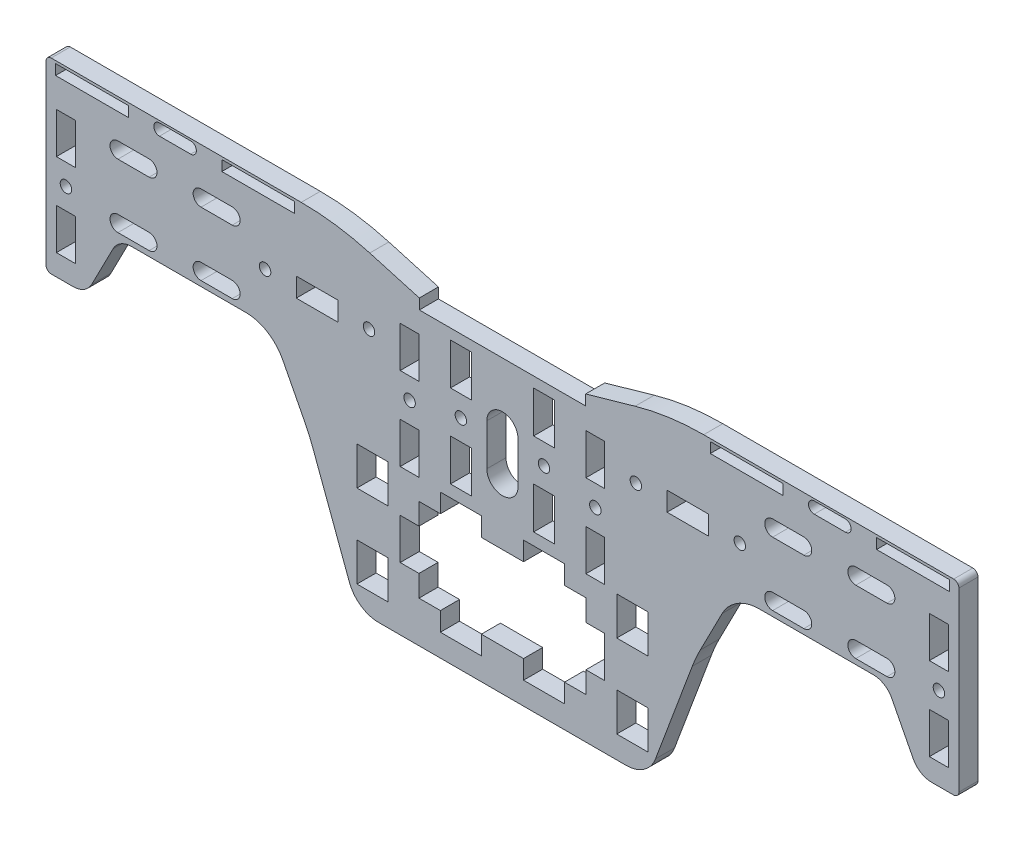
SolidWorks part; units mm, degrees
ref_plane "Front Plane" through (0, 0, 0) normal (0, 0, 1) x (1, 0, 0)
ref_plane "Top Plane" through (0, 0, 0) normal (0, 1, 0) x (1, 0, 0)
ref_plane "Right Plane" through (0, 0, 0) normal (1, 0, 0) x (0, 0, -1)
sketch "Sketch1" plane through (0, 0, 0) normal (0, 0, 1) x (1, 0, 0)
  line L0 (25.4, 66.675) -> (-25.4, 66.675) construction
  line L1 (25.5, -12.8) -> (18.95, -12.8)
  line L2 (25.5, -12.8) -> (25.5, -6.25)
  line L3 (-25.5, 12.8) -> (-18.95, 12.8)
  line L4 (-25.5, -12.8) -> (-25.5, -6.25)
  line L5 (25.5, -12.8) -> (-25.5, 12.8) construction
  line L6 (25.5, 12.8) -> (-25.5, -12.8) construction
  line L7 (0, 0) -> (0, 66.675) construction
  line L8 (25.4, 63.5) -> (-25.4, 63.5)
  line L9 (95.25, 101.6) -> (95.25, -30.1359) construction
  line L10 (19.05, 101.6) -> (171.45, 101.6) construction
  line L11 (171.45, 122.2375) -> (19.05, 122.2375) construction
  line L12 (171.45, 122.2375) -> (171.45, 80.9625) construction
  line L13 (171.45, 80.9625) -> (112.7125, 80.9625) construction
  line L14 (19.05, 122.2375) -> (19.05, 80.9625) construction
  line L15 (171.45, 122.2375) -> (19.05, 80.9625) construction
  line L16 (171.45, 80.9625) -> (19.05, 122.2375) construction
  line L17 (77.7875, 80.9625) -> (19.05, 80.9625) construction
  line L18 (77.7875, 69.9655) -> (74.2442, 69.9655) construction
  line L19 (112.7125, 69.9655) -> (112.7125, 80.9625) construction
  line L20 (63.246, 14.9745) -> (74.2442, 36.3359) construction
  line L21 (77.7875, 69.9655) -> (77.7875, 80.9625) construction
  line L22 (112.7125, 69.9655) -> (77.7875, 80.9625) construction
  line L23 (112.7125, 80.9625) -> (77.7875, 69.9655) construction
  line L24 (116.2558, 36.3359) -> (74.2442, 36.3359) construction
  line L25 (116.2558, 36.3359) -> (116.2558, 69.9655) construction
  line L26 (116.2558, 69.9655) -> (112.7125, 69.9655) construction
  line L27 (74.2442, 36.3359) -> (74.2442, 69.9655) construction
  line L28 (116.2558, 36.3359) -> (74.2442, 69.9655) construction
  line L29 (116.2558, 69.9655) -> (74.2442, 36.3359) construction
  line L30 (127.254, -75.2463) -> (63.246, -75.2463) construction
  line L31 (127.254, -75.2463) -> (127.254, 14.9745) construction
  line L32 (127.254, 14.9745) -> (63.246, 14.9745) construction
  line L33 (63.246, -75.2463) -> (63.246, 14.9745) construction
  line L34 (127.254, -75.2463) -> (63.246, 14.9745) construction
  line L35 (127.254, 14.9745) -> (63.246, -75.2463) construction
  line L36 (127.254, 14.9745) -> (116.2558, 36.3359) construction
  line L37 (74.2442, 59.7801) -> (116.2558, 59.7801) construction
  line L38 (74.2442, 40.3491) -> (116.2558, 40.3491) construction
  line L39 (-6.45, 12.8) -> (6.45, 12.8)
  line L40 (-6.45, 18.542) -> (-18.95, 18.542)
  line L41 (-6.45, 18.542) -> (-6.45, 12.8)
  line L42 (18.95, 18.542) -> (18.95, 12.8)
  line L43 (-18.95, 18.542) -> (-18.95, 12.8)
  line L44 (-6.45, 18.542) -> (-18.95, 12.8) construction
  line L45 (-6.45, 12.8) -> (-18.95, 18.542) construction
  line L46 (-25.5, 0) -> (25.5, 0) construction
  line L47 (6.45, 18.542) -> (6.45, 12.8)
  line L48 (6.45, 18.542) -> (18.95, 12.8) construction
  line L49 (6.45, 12.8) -> (18.95, 18.542) construction
  line L50 (6.45, 18.542) -> (18.95, 18.542)
  line L51 (18.95, 12.8) -> (25.5, 12.8)
  line L52 (44.45, -6.858) -> (34.925, -18.542) construction
  line L53 (44.45, 18.542) -> (34.925, 18.542)
  line L54 (44.45, 18.542) -> (44.45, 6.858)
  line L55 (44.45, 6.858) -> (34.925, 6.858)
  line L56 (34.925, 18.542) -> (34.925, 6.858)
  line L57 (44.45, 18.542) -> (34.925, 6.858) construction
  line L58 (44.45, 6.858) -> (34.925, 18.542) construction
  line L59 (44.45, -18.542) -> (34.925, -6.858) construction
  line L60 (34.925, -18.542) -> (34.925, -6.858)
  line L61 (44.45, -6.858) -> (34.925, -6.858)
  line L62 (44.45, -18.542) -> (44.45, -6.858)
  line L63 (44.45, -18.542) -> (34.925, -18.542)
  line L64 (-44.45, -18.542) -> (-34.925, -6.858) construction
  line L65 (-44.45, 6.858) -> (-34.925, 18.542) construction
  line L66 (-44.45, 18.542) -> (-34.925, 6.858) construction
  line L67 (0, 0) -> (0, -30.1681) construction
  line L68 (-44.45, -6.858) -> (-34.925, -18.542) construction
  line L69 (-44.45, -18.542) -> (-34.925, -18.542)
  line L70 (-44.45, -18.542) -> (-44.45, -6.858)
  line L71 (-44.45, -6.858) -> (-34.925, -6.858)
  line L72 (-34.925, -18.542) -> (-34.925, -6.858)
  line L73 (-34.925, 18.542) -> (-34.925, 6.858)
  line L74 (6.45, -12.8) -> (18.95, -18.542) construction
  line L75 (6.45, -18.542) -> (18.95, -12.8) construction
  line L76 (-6.45, -12.8) -> (-18.95, -18.542) construction
  line L77 (-6.45, -18.542) -> (-18.95, -12.8) construction
  line L78 (-44.45, 6.858) -> (-34.925, 6.858)
  line L79 (44.45, -25.4) -> (-44.45, -25.4)
  line L80 (-44.45, 18.542) -> (-44.45, 6.858)
  line L81 (-44.45, 18.542) -> (-34.925, 18.542)
  line L82 (-12.7, 63.5) -> (-12.7, 47.625) construction
  line L83 (-15.875, 22.225) -> (-9.525, 22.225)
  line L84 (-15.875, 47.625) -> (-9.525, 47.625)
  line L85 (-15.875, 47.625) -> (-15.875, 60.325)
  line L86 (-15.875, 60.325) -> (-9.525, 60.325)
  line L87 (-9.525, 47.625) -> (-9.525, 60.325)
  line L88 (-15.875, 47.625) -> (-9.525, 60.325) construction
  line L89 (-15.875, 60.325) -> (-9.525, 47.625) construction
  line L90 (6.45, -18.542) -> (18.95, -18.542)
  line L91 (6.45, -18.542) -> (6.45, -12.8)
  line L92 (-18.95, -18.542) -> (-18.95, -12.8)
  line L93 (18.95, -18.542) -> (18.95, -12.8)
  line L94 (-6.45, -18.542) -> (-6.45, -12.8)
  line L95 (-6.45, -18.542) -> (-18.95, -18.542)
  line L96 (-18.95, -12.8) -> (-25.5, -12.8)
  line L97 (6.45, -12.8) -> (-6.45, -12.8)
  line L98 (-25.5, 6.25) -> (-25.5, 12.8)
  line L99 (-31.242, -6.25) -> (-25.5, -6.25)
  line L100 (-31.242, -6.25) -> (-31.242, 6.25)
  line L101 (-31.242, 6.25) -> (-25.5, 6.25)
  line L102 (31.242, 6.25) -> (25.5, 6.25)
  line L103 (-31.242, -6.25) -> (-25.5, 6.25) construction
  line L104 (-31.242, 6.25) -> (-25.5, -6.25) construction
  line L105 (31.242, -6.25) -> (25.5, -6.25)
  line L106 (31.242, -6.25) -> (25.5, 6.25) construction
  line L107 (31.242, 6.25) -> (25.5, -6.25) construction
  line L108 (31.242, -6.25) -> (31.242, 6.25)
  line L109 (25.5, 6.25) -> (25.5, 12.8)
  line L110 (-15.875, 22.225) -> (-15.875, 34.925)
  line L111 (-15.875, 34.925) -> (-9.525, 34.925)
  line L112 (82.55, 59.7801) -> (92.075, 59.7801) construction
  line L113 (82.55, 62.1931) -> (92.075, 62.1931)
  line L114 (82.55, 57.3671) -> (92.075, 57.3671)
  line L115 (82.55, 40.3491) -> (92.075, 40.3491) construction
  line L116 (82.55, 42.7621) -> (92.075, 42.7621)
  line L117 (82.55, 37.9361) -> (92.075, 37.9361)
  line L118 (107.95, 59.7801) -> (117.475, 59.7801) construction
  line L119 (107.95, 62.1931) -> (117.475, 62.1931)
  line L120 (107.95, 57.3671) -> (117.475, 57.3671)
  line L121 (107.95, 40.3491) -> (117.475, 40.3491) construction
  line L122 (107.95, 42.7621) -> (117.475, 42.7621)
  line L123 (107.95, 37.9361) -> (117.475, 37.9361)
  line L124 (63.8955, 73.1405) -> (128.9432, 73.1405) construction
  line L125 (63.5, 73.1405) -> (76.2, 73.1405)
  line L126 (63.5, 73.1405) -> (63.5, 69.9655)
  line L127 (114.3, 73.1405) -> (127, 73.1405)
  line L128 (63.5, 69.9655) -> (76.2, 69.9655)
  line L129 (63.5, 69.9655) -> (76.2, 73.1405) construction
  line L130 (63.5, 73.1405) -> (76.2, 69.9655) construction
  line L131 (114.3, 69.9655) -> (127, 69.9655)
  line L132 (76.2, 73.1405) -> (85.725, 73.1405)
  line L133 (76.2, 69.9655) -> (85.725, 69.9655)
  line L134 (85.725, 73.1405) -> (85.725, 69.9655)
  line L135 (114.3, 73.1405) -> (114.3, 69.9655)
  line L136 (127, 73.1405) -> (136.525, 73.1405)
  line L137 (136.525, 73.1405) -> (136.525, 69.9655)
  line L138 (127, 69.9655) -> (136.525, 69.9655)
  line L139 (-28.371, 0) -> (-28.371, 63.5) construction
  line L140 (-31.242, 44.55) -> (-25.5, 44.55)
  line L141 (-31.242, 31.65) -> (-25.5, 31.65)
  line L142 (-31.242, 31.65) -> (-31.242, 19.15)
  line L143 (-31.242, 19.15) -> (-25.5, 19.15)
  line L144 (-25.5, 31.65) -> (-25.5, 19.15)
  line L145 (-31.242, 31.65) -> (-25.5, 19.15) construction
  line L146 (-31.242, 19.15) -> (-25.5, 31.65) construction
  line L147 (-31.242, 57.05) -> (-31.242, 44.55)
  line L148 (-31.242, 57.05) -> (-25.5, 57.05)
  line L149 (-25.5, 57.05) -> (-25.5, 44.55)
  line L150 (28.371, 0) -> (28.371, 63.5) construction
  line L151 (31.242, 19.15) -> (25.5, 31.65) construction
  line L152 (31.242, 31.65) -> (25.5, 19.15) construction
  line L153 (25.5, 57.05) -> (25.5, 44.55)
  line L154 (31.242, 57.05) -> (25.5, 57.05)
  line L155 (31.242, 57.05) -> (31.242, 44.55)
  line L156 (25.5, 31.65) -> (25.5, 19.15)
  line L157 (31.242, 19.15) -> (25.5, 19.15)
  line L158 (31.242, 31.65) -> (31.242, 19.15)
  line L159 (31.242, 31.65) -> (25.5, 31.65)
  line L160 (31.242, 44.55) -> (25.5, 44.55)
  line L161 (50.8, 73.9342) -> (139.446, 73.9342)
  line L162 (25.4, 63.5) -> (25.4, 66.675)
  line L163 (25.4, 66.675) -> (50.8, 73.9342)
  line L164 (44.45, -25.4) -> (59.0461, 13.7533)
  line L165 (70.6731, 36.3359) -> (117.1876, 36.3359)
  line L166 (59.0461, 13.7533) -> (70.6731, 36.3359)
  line L167 (133.35, 73.9342) -> (133.35, 48.6342) construction
  line L168 (60.4232, 16.4279) -> (71.4214, 37.7893) construction
  line L169 (130.429, 35.7342) -> (136.271, 35.7342)
  line L170 (-25.4, 63.5) -> (-25.4, 66.675)
  line L171 (-25.4, 66.675) -> (-50.8, 73.9342)
  line L172 (-63.5, 73.1405) -> (-76.2, 69.9655) construction
  line L173 (-63.5, 69.9655) -> (-76.2, 73.1405) construction
  line L174 (-63.8955, 73.1405) -> (-128.9432, 73.1405) construction
  line L175 (-74.2442, 40.3491) -> (-116.2558, 40.3491) construction
  line L176 (-74.2442, 59.7801) -> (-116.2558, 59.7801) construction
  line L177 (-127.254, 14.9745) -> (-116.2558, 36.3359) construction
  line L178 (-127.254, 14.9745) -> (-63.246, -75.2463) construction
  line L179 (-127.254, -75.2463) -> (-63.246, 14.9745) construction
  line L180 (-63.246, -75.2463) -> (-63.246, 14.9745) construction
  line L181 (-127.254, 14.9745) -> (-63.246, 14.9745) construction
  line L182 (-127.254, -75.2463) -> (-127.254, 14.9745) construction
  line L183 (-127.254, -75.2463) -> (-63.246, -75.2463) construction
  line L184 (-116.2558, 69.9655) -> (-74.2442, 36.3359) construction
  line L185 (-116.2558, 36.3359) -> (-74.2442, 69.9655) construction
  line L186 (-74.2442, 36.3359) -> (-74.2442, 69.9655) construction
  line L187 (-116.2558, 69.9655) -> (-112.7125, 69.9655) construction
  line L188 (-116.2558, 36.3359) -> (-116.2558, 69.9655) construction
  line L189 (-116.2558, 36.3359) -> (-74.2442, 36.3359) construction
  line L190 (-112.7125, 80.9625) -> (-77.7875, 69.9655) construction
  line L191 (-112.7125, 69.9655) -> (-77.7875, 80.9625) construction
  line L192 (-77.7875, 69.9655) -> (-77.7875, 80.9625) construction
  line L193 (-63.246, 14.9745) -> (-74.2442, 36.3359) construction
  line L194 (-112.7125, 69.9655) -> (-112.7125, 80.9625) construction
  line L195 (-77.7875, 69.9655) -> (-74.2442, 69.9655) construction
  line L196 (-77.7875, 80.9625) -> (-19.05, 80.9625) construction
  line L197 (-171.45, 80.9625) -> (-19.05, 122.2375) construction
  line L198 (-171.45, 122.2375) -> (-19.05, 80.9625) construction
  line L199 (-171.45, 80.9625) -> (-112.7125, 80.9625) construction
  line L200 (-171.45, 122.2375) -> (-171.45, 80.9625) construction
  line L201 (-171.45, 122.2375) -> (-19.05, 122.2375) construction
  line L202 (-19.05, 101.6) -> (-171.45, 101.6) construction
  line L203 (-95.25, 101.6) -> (-95.25, -30.1359) construction
  line L204 (130.429, 61.1342) -> (136.271, 61.1342)
  line L205 (130.429, 61.1342) -> (130.429, 48.6342)
  line L206 (-59.0461, 13.7533) -> (-70.6731, 36.3359)
  line L207 (-70.6731, 36.3359) -> (-117.1876, 36.3359)
  line L208 (-44.45, -25.4) -> (-59.0461, 13.7533)
  line L209 (-50.8, 73.9342) -> (-139.446, 73.9342)
  line L210 (-127, 69.9655) -> (-136.525, 69.9655)
  line L211 (-136.525, 73.1405) -> (-136.525, 69.9655)
  line L212 (-127, 73.1405) -> (-136.525, 73.1405)
  line L213 (-114.3, 73.1405) -> (-114.3, 69.9655)
  line L214 (-85.725, 73.1405) -> (-85.725, 69.9655)
  line L215 (-76.2, 69.9655) -> (-85.725, 69.9655)
  line L216 (-76.2, 73.1405) -> (-85.725, 73.1405)
  line L217 (-114.3, 69.9655) -> (-127, 69.9655)
  line L218 (-63.5, 69.9655) -> (-76.2, 69.9655)
  line L219 (-114.3, 73.1405) -> (-127, 73.1405)
  line L220 (-63.5, 73.1405) -> (-63.5, 69.9655)
  line L221 (-63.5, 73.1405) -> (-76.2, 73.1405)
  line L222 (-107.95, 40.3491) -> (-117.475, 40.3491) construction
  line L223 (-107.95, 42.7621) -> (-117.475, 42.7621)
  line L224 (-107.95, 37.9361) -> (-117.475, 37.9361)
  line L225 (-107.95, 59.7801) -> (-117.475, 59.7801) construction
  line L226 (-107.95, 62.1931) -> (-117.475, 62.1931)
  line L227 (-107.95, 57.3671) -> (-117.475, 57.3671)
  line L228 (-82.55, 40.3491) -> (-92.075, 40.3491) construction
  line L229 (-82.55, 42.7621) -> (-92.075, 42.7621)
  line L230 (-82.55, 37.9361) -> (-92.075, 37.9361)
  line L231 (-82.55, 59.7801) -> (-92.075, 59.7801) construction
  line L232 (-82.55, 62.1931) -> (-92.075, 62.1931)
  line L233 (-82.55, 57.3671) -> (-92.075, 57.3671)
  line L234 (-19.05, 122.2375) -> (-19.05, 80.9625) construction
  line L235 (-25.5, 44.55) -> (-25.5, 31.65) construction
  line L236 (25.5, 31.65) -> (25.5, 44.55) construction
  line L237 (-25.5, 38.1) -> (25.5, 38.1) construction
  line L238 (-9.525, 22.225) -> (-9.525, 34.925)
  line L239 (-15.875, 22.225) -> (-9.525, 34.925) construction
  line L240 (-15.875, 34.925) -> (-9.525, 22.225) construction
  line L241 (-12.7, 34.925) -> (-12.7, 18.542) construction
  line L242 (-12.7, 47.625) -> (-12.7, 34.925) construction
  line L243 (12.7, 47.625) -> (12.7, 34.925) construction
  line L244 (15.875, 34.925) -> (9.525, 22.225) construction
  line L245 (15.875, 22.225) -> (9.525, 34.925) construction
  line L246 (15.875, 60.325) -> (9.525, 47.625) construction
  line L247 (15.875, 47.625) -> (9.525, 60.325) construction
  line L248 (9.525, 22.225) -> (9.525, 34.925)
  line L249 (15.875, 34.925) -> (9.525, 34.925)
  line L250 (15.875, 22.225) -> (15.875, 34.925)
  line L251 (9.525, 47.625) -> (9.525, 60.325)
  line L252 (15.875, 60.325) -> (9.525, 60.325)
  line L253 (15.875, 47.625) -> (15.875, 60.325)
  line L254 (15.875, 47.625) -> (9.525, 47.625)
  line L255 (15.875, 22.225) -> (9.525, 22.225)
  line L256 (-116.2558, 50.75) -> (-74.2442, 50.75) construction
  line L257 (-85.725, 71.553) -> (-114.3, 71.553) construction
  line L258 (-95.25, 71.553) -> (-104.775, 71.553) construction
  line L259 (-95.25, 69.8004) -> (-104.775, 69.8004)
  line L260 (-95.25, 73.3056) -> (-104.775, 73.3056)
  line L261 (50.292, 53.671) -> (50.292, 47.829)
  line L262 (-62.992, 53.671) -> (-50.292, 53.671)
  line L263 (-62.992, 53.671) -> (-62.992, 47.829)
  line L264 (-62.992, 47.829) -> (-50.292, 47.829)
  line L265 (-50.292, 53.671) -> (-50.292, 47.829)
  line L266 (-62.992, 53.671) -> (-50.292, 47.829) construction
  line L267 (-62.992, 47.829) -> (-50.292, 53.671) construction
  line L268 (62.992, 53.671) -> (50.292, 47.829) construction
  line L269 (62.992, 47.829) -> (50.292, 53.671) construction
  line L270 (62.992, 47.829) -> (50.292, 47.829)
  line L271 (62.992, 53.671) -> (62.992, 47.829)
  line L272 (62.992, 53.671) -> (50.292, 53.671)
  line L273 (95.25, 71.553) -> (104.775, 71.553) construction
  line L274 (95.25, 69.8004) -> (104.775, 69.8004)
  line L275 (95.25, 73.3056) -> (104.775, 73.3056)
  line L276 (-56.642, 47.829) -> (-56.642, 53.671) construction
  line L277 (130.429, 48.6342) -> (136.271, 48.6342)
  line L278 (136.271, 61.1342) -> (136.271, 48.6342)
  line L279 (130.429, 61.1342) -> (136.271, 48.6342) construction
  line L280 (130.429, 48.6342) -> (136.271, 61.1342) construction
  line L281 (130.429, 35.7342) -> (130.429, 23.2342)
  line L282 (130.429, 23.2342) -> (136.271, 23.2342)
  line L283 (136.271, 35.7342) -> (136.271, 23.2342)
  line L284 (133.35, 35.7342) -> (133.35, 23.2342) construction
  line L285 (130.429, 35.7342) -> (136.271, 23.2342) construction
  line L286 (130.429, 23.2342) -> (136.271, 35.7342) construction
  line L287 (133.35, 35.7342) -> (133.35, 27.5161) construction
  line L288 (133.35, 35.7342) -> (133.35, 48.6342) construction
  line L289 (139.446, 73.9342) -> (139.446, 16.7842)
  line L290 (139.446, 16.7842) -> (127.254, 16.7842)
  line L291 (127.254, 16.7842) -> (117.1876, 36.3359)
  line L292 (-127.254, 16.7842) -> (-117.1876, 36.3359)
  line L293 (-139.446, 16.7842) -> (-127.254, 16.7842)
  line L294 (-139.446, 73.9342) -> (-139.446, 16.7842)
  line L295 (-133.35, 35.7342) -> (-133.35, 48.6342) construction
  line L296 (-133.35, 35.7342) -> (-133.35, 27.5161) construction
  line L297 (-130.429, 23.2342) -> (-136.271, 35.7342) construction
  line L298 (-130.429, 35.7342) -> (-136.271, 23.2342) construction
  line L299 (-133.35, 35.7342) -> (-133.35, 23.2342) construction
  line L300 (-130.429, 48.6342) -> (-136.271, 61.1342) construction
  line L301 (-130.429, 61.1342) -> (-136.271, 48.6342) construction
  line L302 (-136.271, 35.7342) -> (-136.271, 23.2342)
  line L303 (-130.429, 23.2342) -> (-136.271, 23.2342)
  line L304 (-130.429, 35.7342) -> (-130.429, 23.2342)
  line L305 (-136.271, 61.1342) -> (-136.271, 48.6342)
  line L306 (-130.429, 48.6342) -> (-136.271, 48.6342)
  line L307 (-130.429, 61.1342) -> (-130.429, 48.6342)
  line L308 (-130.429, 61.1342) -> (-136.271, 61.1342)
  line L309 (-130.429, 35.7342) -> (-136.271, 35.7342)
  circle A0 centre (82.55, 59.7801) radius 2.413 construction
  circle A1 centre (107.95, 59.7801) radius 2.413 construction
  circle A2 centre (82.55, 40.3491) radius 2.413 construction
  circle A3 centre (107.95, 40.3491) radius 2.413 construction
  arc A4 (82.55, 62.1931) -> (82.55, 57.3671) centre (82.55, 59.7801) ccw
  arc A5 (92.075, 57.3671) -> (92.075, 62.1931) centre (92.075, 59.7801) ccw
  arc A6 (82.55, 42.7621) -> (82.55, 37.9361) centre (82.55, 40.3491) ccw
  arc A7 (92.075, 37.9361) -> (92.075, 42.7621) centre (92.075, 40.3491) ccw
  arc A8 (107.95, 62.1931) -> (107.95, 57.3671) centre (107.95, 59.7801) ccw
  arc A9 (117.475, 57.3671) -> (117.475, 62.1931) centre (117.475, 59.7801) ccw
  arc A10 (107.95, 42.7621) -> (107.95, 37.9361) centre (107.95, 40.3491) ccw
  arc A11 (117.475, 37.9361) -> (117.475, 42.7621) centre (117.475, 40.3491) ccw
  circle A12 centre (-107.95, 40.3491) radius 2.413 construction
  circle A13 centre (-82.55, 40.3491) radius 2.413 construction
  circle A14 centre (-107.95, 59.7801) radius 2.413 construction
  circle A15 centre (-82.55, 59.7801) radius 2.413 construction
  arc A16 (-107.95, 42.7621) -> (-107.95, 37.9361) centre (-107.95, 40.3491) cw
  arc A17 (-117.475, 37.9361) -> (-117.475, 42.7621) centre (-117.475, 40.3491) cw
  arc A18 (-107.95, 62.1931) -> (-107.95, 57.3671) centre (-107.95, 59.7801) cw
  arc A19 (-117.475, 57.3671) -> (-117.475, 62.1931) centre (-117.475, 59.7801) cw
  arc A20 (-82.55, 42.7621) -> (-82.55, 37.9361) centre (-82.55, 40.3491) cw
  arc A21 (-92.075, 37.9361) -> (-92.075, 42.7621) centre (-92.075, 40.3491) cw
  arc A22 (-82.55, 62.1931) -> (-82.55, 57.3671) centre (-82.55, 59.7801) cw
  arc A23 (-92.075, 57.3671) -> (-92.075, 62.1931) centre (-92.075, 59.7801) cw
  circle A24 centre (0, 101.6) radius 34.925 construction
  circle A25 centre (28.371, 38.1) radius 1.7526
  circle A26 centre (-28.371, 38.1) radius 1.7526
  circle A27 centre (-12.7, 41.275) radius 1.7526
  circle A28 centre (12.7, 41.275) radius 1.7526
  arc A29 (-95.25, 69.8004) -> (-95.25, 73.3056) centre (-95.25, 71.553) ccw
  arc A30 (-104.775, 73.3056) -> (-104.775, 69.8004) centre (-104.775, 71.553) ccw
  arc A31 (95.25, 69.8004) -> (95.25, 73.3056) centre (95.25, 71.553) cw
  arc A32 (104.775, 73.3056) -> (104.775, 69.8004) centre (104.775, 71.553) cw
  circle A33 centre (-72.517, 50.75) radius 1.7526
  circle A34 centre (-40.767, 50.75) radius 1.7526
  circle A35 centre (40.767, 50.75) radius 1.7526
  circle A36 centre (72.517, 50.75) radius 1.7526
  circle A37 centre (133.35, 42.1842) radius 1.7526
  circle A38 centre (-133.35, 42.1842) radius 1.7526
  point P0 (0, 0)
  point P9 (0, 66.675)
  point P14 (0, 63.5)
  point P22 (95.25, 75.464)
  point P27 (95.25, 53.1507)
  point P45 (39.6875, 12.7)
  point P49 (-12.7, 15.671)
  point P60 (12.7, 15.671)
  point P63 (0, 15.671)
  point P70 (39.6875, -12.7)
  point P79 (-39.6875, -12.7)
  point P80 (-39.6875, 12.7)
  point P83 (-12.7, 53.975)
  point P97 (-12.7, 28.575)
  point P100 (0, -15.671)
  point P101 (12.7, -15.671)
  point P102 (-12.7, -15.671)
  point P104 (-28.371, 0)
  point P113 (28.371, 0)
  point P118 (0, -25.4)
  point P119 (87.3125, 59.7801)
  point P124 (87.3125, 40.3491)
  point P135 (112.7125, 59.7801)
  point P140 (112.7125, 40.3491)
  point P146 (69.85, 71.553)
  point P161 (-28.371, 25.4)
  point P180 (28.371, 25.4)
  point P241 (-69.85, 71.553)
  point P243 (-112.7125, 40.3491)
  point P249 (-112.7125, 59.7801)
  point P255 (-87.3125, 40.3491)
  point P261 (-87.3125, 59.7801)
  point P266 (-95.25, 53.1507)
  point P267 (-95.25, 75.464)
  point P292 (12.7, 28.575)
  point P293 (12.7, 53.975)
  point P300 (-100.0125, 71.553)
  point P305 (-56.642, 50.75)
  point P316 (100.0125, 71.553)
  point P331 (133.35, 54.8842)
  point P340 (133.35, 29.4842)
  point P364 (-133.35, 29.4842)
  point P365 (-133.35, 54.8842)
  dimension "D17" = 4.826
  dimension "D33" = 2.413
  dimension "D34" = 2.413
  dimension "D53" = 69.85
  dimension "D56" = 3.5052
  dimension "D61" = 3.5052
  dimension "D64" = 1.7526
  dimension "D69" = 3.5052
  dimension "D74" = 3.5052
  dimension "D1" = 25.6
  dimension "D2" = 51
  dimension "D3" = 50.8
  dimension "D4" = 66.675
  dimension "D5" = 3.175
  dimension "D6" = 152.4
  dimension "D7" = 41.275
  dimension "D9" = 19.05
  dimension "D10" = 10.997
  dimension "D11" = 42.0116
  dimension "D12" = 33.6296
  dimension "D13" = 64.008
  dimension "D14" = 90.2208
  dimension "D15" = 21.3614
  dimension "D16" = 10.1854
  dimension "D18" = 12.7
  dimension "D19" = 19.431
  dimension "D21" = 12.7
  dimension "D22" = 5.742
  dimension "D23" = 12.5
  dimension "D24" = 9.525
  dimension "D25" = 11.684
  dimension "D26" = 39.6875
  dimension "D27" = 6.35
  dimension "D28" = 5.742
  dimension "D29" = 12.5
  dimension "D30" = 25.4
  dimension "D31" = 88.9
  dimension "D32" = 9.525
  dimension "D35" = 9.525
  dimension "D37" = 34.925
  dimension "D38" = 3.175
  dimension "D39" = 3.175
  dimension "D40" = 12.7
  dimension "D41" = 25.4
  dimension "D42" = 9.525
  dimension "D44" = 5.742
  dimension "D45" = 12.5
  dimension "D46" = 25.4
  dimension "D48" = 1.5875
  dimension "D49" = 25.4
  dimension "D51" = 12.192
  dimension "D52" = 3.175
  dimension "D54" = 101.6
  dimension "D55" = 25.4
  dimension "D57" = 9.525
  dimension "D58" = 12.7
  dimension "D59" = 12.7
  dimension "D63" = 9.525
  dimension "D65" = 19.05
  dimension "D66" = 12.7
  dimension "D67" = 5.842
  dimension "D68" = 15.875
  dimension "D70" = 5.842
  dimension "D71" = 12.5
  dimension "D73" = 19.05
  dimension "D75" = 38.1
  dimension "D76" = 12.7
  dimension "D50" = 3.175
  dimension "D20" = 2
  dimension "D36" = 2
  dimension "D43" = 2
  dimension "D47" = 2
  dimension "D60" = 2
  dimension "D72" = 2
extrude "Boss-Extrude1" add sketch "Sketch1" along normal blind 5.842
fillet "Fillet1" radius 12.7 2 edges at (70.6731, 36.3359, 2.921) (-70.6731, 36.3359, 2.921)
fillet "Fillet2" radius 9.525 2 edges at (-44.45, -25.4, 2.921) (44.45, -25.4, 2.921)
fillet "Fillet4" radius 76.2 2 edges at (50.8, 73.9342, 2.921) (-50.8, 73.9342, 2.921)
fillet "Fillet5" radius 50.8 2 edges at (59.0461, 13.7533, 2.921) (-59.0461, 13.7533, 2.921)
sketch "Sketch2" [suppressed] plane through (0, 0, 5.842) normal (0, 0, 1) x (1, 0, 0)
  line L0 (44.45, 6.858) -> (44.45, 18.542) construction
  line L1 (-44.45, 18.542) -> (-34.925, 18.542)
  line L2 (-44.45, 18.542) -> (-44.45, -18.542)
  line L3 (-44.45, -18.542) -> (-34.925, -18.542)
  line L4 (-34.925, 18.542) -> (-34.925, -18.542)
  line L5 (34.925, -18.542) -> (44.45, -18.542)
  line L6 (34.925, -18.542) -> (34.925, 18.542)
  line L7 (34.925, 18.542) -> (44.45, 18.542)
  line L8 (44.45, -18.542) -> (44.45, 18.542)
extrude "Boss-Extrude2" [suppressed] add sketch "Sketch2" against normal up to surface (5.842 mm away) up to face at (-133.35, 54.8842, 0)
sketch "Sketch3" [suppressed] plane through (0, 0, 5.842) normal (0, 0, 1) x (1, 0, 0)
  line L0 (0, 63.5) -> (0, -25.4) construction
  line L1 (-77.0183, 57.907) -> (-37.2922, 57.907)
  line L2 (-77.0183, 57.907) -> (-77.0183, 44.7899)
  line L3 (-77.0183, 44.7899) -> (-37.2922, 44.7899)
  line L4 (-37.2922, 57.907) -> (-37.2922, 44.7899)
  line L5 (-31.242, 57.05) -> (-25.5, 57.05)
  line L6 (-31.242, 57.05) -> (-31.242, 19.15)
  line L8 (-25.5, 57.05) -> (-25.5, 19.15)
  line L9 (25.4, 63.5) -> (-25.4, 63.5) construction
  line L10 (-37.8355, -25.4) -> (37.8355, -25.4) construction
  line L11 (25.5, 57.05) -> (25.5, 19.15)
  line L13 (31.242, 57.05) -> (31.242, 19.15)
  line L14 (31.242, 57.05) -> (25.5, 57.05)
  line L15 (37.2922, 57.907) -> (37.2922, 44.7899)
  line L16 (77.0183, 44.7899) -> (37.2922, 44.7899)
  line L17 (77.0183, 57.907) -> (77.0183, 44.7899)
  line L18 (77.0183, 57.907) -> (37.2922, 57.907)
  line L21 (-31.242, 19.15) -> (-31.242, -6.25)
  line L22 (-31.242, -6.25) -> (-25.5, -6.25)
  line L23 (-25.5, 19.15) -> (-25.5, -6.25)
  line L24 (25.5, -6.25) -> (31.242, -6.25)
  line L25 (25.5, -6.25) -> (25.5, 19.15)
  line L27 (31.242, -6.25) -> (31.242, 19.15)
extrude "Boss-Extrude3" [suppressed] add sketch "Sketch3" against normal up to surface (5.842 mm away) up to face at (-133.35, 54.8842, 0)
fillet "Fillet6" radius 6.35 4 edges at (-127.254, 16.7842, 2.921) (127.254, 16.7842, 2.921) (117.1876, 36.3359, 2.921) (-117.1876, 36.3359, 2.921)
fillet "Fillet7" radius 1.5875 4 edges at (139.446, 16.7842, 2.921) (139.446, 73.9342, 2.921) (-139.446, 73.9342, 2.921) (-139.446, 16.7842, 2.921)
sketch "Sketch4" [suppressed] plane through (0, 0, 5.842) normal (0, 0, 1) x (1, 0, 0)
  line L0 (0, 63.5) -> (0, 12.8) construction
  line L1 (25.4, 63.5) -> (-25.4, 63.5) construction
  line L2 (6.45, 12.8) -> (-6.45, 12.8) construction
  line L3 (44.45, 63.5) -> (-44.45, 63.5) construction
  line L4 (-50.7, 63.5) -> (-38.2, 60.452) construction
  line L5 (50.7, 60.452) -> (38.2, 60.452)
  line L6 (50.7, 60.452) -> (50.7, 63.5)
  line L7 (50.7, 63.5) -> (38.2, 63.5)
  line L8 (38.2, 60.452) -> (38.2, 63.5)
  line L9 (50.7, 60.452) -> (38.2, 63.5) construction
  line L10 (50.7, 63.5) -> (38.2, 60.452) construction
  line L11 (-50.7, 60.452) -> (-38.2, 63.5) construction
  line L12 (-38.2, 60.452) -> (-38.2, 63.5)
  line L13 (-50.7, 63.5) -> (-38.2, 63.5)
  line L14 (-50.7, 60.452) -> (-50.7, 63.5)
  line L15 (-50.7, 60.452) -> (-38.2, 60.452)
  line L16 (-25.4, 63.5) -> (-25.4, 49.276) construction
  line L17 (23.876, 55.526) -> (26.924, 43.026) construction
  line L18 (-23.876, 43.026) -> (-26.924, 43.026)
  line L19 (-23.876, 43.026) -> (-23.876, 55.526)
  line L20 (-23.876, 55.526) -> (-26.924, 55.526)
  line L21 (-26.924, 43.026) -> (-26.924, 55.526)
  line L22 (-23.876, 43.026) -> (-26.924, 55.526) construction
  line L23 (-23.876, 55.526) -> (-26.924, 43.026) construction
  line L24 (23.876, 43.026) -> (26.924, 55.526) construction
  line L25 (26.924, 43.026) -> (26.924, 55.526)
  line L26 (23.876, 55.526) -> (26.924, 55.526)
  line L27 (23.876, 43.026) -> (23.876, 55.526)
  line L28 (23.876, 43.026) -> (26.924, 43.026)
  point P6 (44.45, 61.976)
  point P9 (0, 63.5)
  point P14 (44.45, 63.5)
  point P19 (-44.45, 61.976)
  point P20 (0, 61.9125)
  dimension "D1" = 88.9
  dimension "D2" = 3.048
  dimension "D3" = 12.5
  dimension "D4" = 12.7
  dimension "D5" = 19.05
  dimension "D6" = 3.048
  dimension "D7" = 12.5
extrude "Cut-Extrude1" [suppressed] cut sketch "Sketch4" against normal through all
sketch "Sketch5" plane through (0, 0, 5.842) normal (0, 0, 1) x (1, 0, 0)
  line L0 (0, 63.5) -> (0, 12.8) construction
  line L1 (25.4, 63.5) -> (-25.4, 63.5) construction
  line L2 (6.45, 12.8) -> (-6.45, 12.8) construction
  line L3 (0, 31.8) -> (0, 44.5) construction
  line L4 (-4.7625, 31.8) -> (-4.7625, 44.5)
  line L5 (4.7625, 31.8) -> (4.7625, 44.5)
  arc A0 (-4.7625, 31.8) -> (4.7625, 31.8) centre (0, 31.8) ccw
  arc A1 (4.7625, 44.5) -> (-4.7625, 44.5) centre (0, 44.5) ccw
  point P8 (0, 38.15)
  dimension "D2" = 4.7625
  dimension "D1" = 12.7
extrude "Cut-Extrude2" cut sketch "Sketch5" against normal through all
fillet "Fillet8" [suppressed] radius 6.35
fillet "Fillet9" [suppressed] radius 1.5875
sketch "Sketch6" [suppressed] plane through (0, 0, 5.842) normal (0, 0, 1) x (1, 0, 0)
  line L0 (51.0259, 6.1954) -> (59.8984, 29.9954) construction
  line L1 (59.3727, 36.8616) -> (55.0063, 25.149)
  line L2 (59.3727, 36.8616) -> (64.7905, 34.8418)
  line L3 (55.0063, 25.149) -> (60.4241, 23.1293)
  line L4 (64.7905, 34.8418) -> (60.4241, 23.1293)
  line L5 (59.3727, 36.8616) -> (60.4241, 23.1293) construction
  line L6 (55.0063, 25.149) -> (64.7905, 34.8418) construction
  line L7 (73.5382, 11.3568) -> (37.3861, 24.8341) construction
  line L8 (50.5002, 13.0616) -> (51.5516, -0.6707) construction
  line L9 (46.1338, 1.349) -> (55.918, 11.0419) construction
  line L10 (51.5516, -0.6707) -> (55.918, 11.0419)
  line L11 (50.5002, 13.0616) -> (55.918, 11.0419)
  line L12 (46.1338, 1.349) -> (51.5516, -0.6707)
  line L13 (46.1338, 1.349) -> (50.5002, 13.0616)
  line L14 (46.7605, -19.2022) -> (57.9923, 10.9265) construction
  circle A0 centre (55.4622, 18.0954) radius 1.7526
  point P10 (55.4622, 18.0954)
  dimension "D1" = 3.5052
  dimension "D2" = 25.4
  dimension "D3" = 5.782
  dimension "D4" = 12.5
